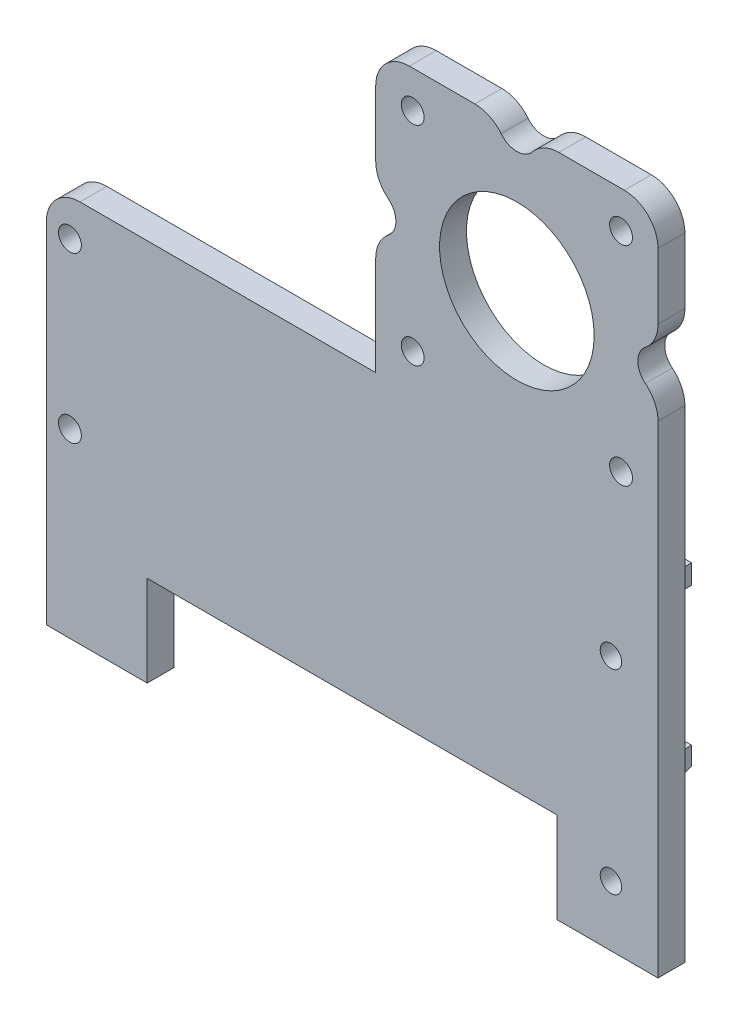
SolidWorks part; units mm, degrees
note: The reader was unsure of these and kept them because the rebuilt part matched: shared geometry of "草图1<4>", "草图1<5>".
ref_plane "前视基准面" through (0, 0, 0) normal (0, 0, 1) x (1, 0, 0)
ref_plane "上视基准面" through (0, 0, 0) normal (0, 1, 0) x (1, 0, 0)
ref_plane "右视基准面" through (0, 0, 0) normal (1, 0, 0) x (0, 0, -1)
sketch "草图1" plane through (0, 0, 0) normal (0, 0, 1) x (1, 0, 0)
  line L0 (0, -1000) -> (0, 49000) construction
  line L1 (-3.2, 10) -> (-3.2, 8.5) construction
  line L2 (-10, -10) -> (10, -10) construction
  line L3 (-10, -10) -> (-10, 10) construction
  line L4 (-10, 10) -> (10, 10) construction
  line L5 (-1000, 0) -> (49000, 0) construction
  line L6 (10, -10) -> (10, 10) construction
  line L7 (-10, -10) -> (10, 10) construction
  line L8 (-10, 10) -> (10, -10) construction
  line L9 (-3.2, 8.5) -> (-5.5, 8.5) construction
  line L10 (-5.5, 8.5) -> (-5.5, 6.7) construction
  line L11 (-5.5, 6.7) -> (-2.8, 4) construction
  line L12 (-2.8, 4) -> (2.8, 4) construction
  line L13 (5.5, 6.7) -> (2.8, 4) construction
  line L14 (5.5, 8.5) -> (5.5, 6.7) construction
  line L15 (3.2, 8.5) -> (5.5, 8.5) construction
  line L16 (3.2, 10) -> (3.2, 8.5) construction
  line L17 (8.5, 3.2) -> (8.5, 5.5) construction
  line L18 (8.5, 5.5) -> (6.7, 5.5) construction
  line L19 (6.7, 5.5) -> (4, 2.8) construction
  line L20 (4, 2.8) -> (4, -2.8) construction
  line L21 (6.7, -5.5) -> (4, -2.8) construction
  line L22 (8.5, -5.5) -> (6.7, -5.5) construction
  line L23 (8.5, -3.2) -> (8.5, -5.5) construction
  line L24 (10, 3.2) -> (8.5, 3.2) construction
  line L25 (10, -3.2) -> (8.5, -3.2) construction
  line L26 (3.2, -8.5) -> (5.5, -8.5) construction
  line L27 (5.5, -8.5) -> (5.5, -6.7) construction
  line L28 (5.5, -6.7) -> (2.8, -4) construction
  line L29 (2.8, -4) -> (-2.8, -4) construction
  line L30 (-5.5, -6.7) -> (-2.8, -4) construction
  line L31 (-5.5, -8.5) -> (-5.5, -6.7) construction
  line L32 (-3.2, -8.5) -> (-5.5, -8.5) construction
  line L33 (3.2, -10) -> (3.2, -8.5) construction
  line L34 (-3.2, -10) -> (-3.2, -8.5) construction
  line L35 (-8.5, -3.2) -> (-8.5, -5.5) construction
  line L36 (-8.5, -5.5) -> (-6.7, -5.5) construction
  line L37 (-6.7, -5.5) -> (-4, -2.8) construction
  line L38 (-4, -2.8) -> (-4, 2.8) construction
  line L39 (-6.7, 5.5) -> (-4, 2.8) construction
  line L40 (-8.5, 5.5) -> (-6.7, 5.5) construction
  line L41 (-8.5, 3.2) -> (-8.5, 5.5) construction
  line L42 (-10, -3.2) -> (-8.5, -3.2) construction
  line L43 (-10, 3.2) -> (-8.5, 3.2) construction
  line L44 (-10, 10) -> (-50, 10) construction
  line L45 (-50, 10) -> (-50, -10) construction
  line L46 (-50, -10) -> (-10, -10) construction
  line L47 (-50, -10) -> (21, -10)
  line L48 (-21, 30) -> (21, 30) construction
  line L49 (-21, 30) -> (-21, 44.755)
  line L50 (-16, 72) -> (-6.245, 72)
  line L51 (21, 30) -> (21, 44.755)
  line L52 (-21, 30) -> (21, 72) construction
  line L53 (-21, 72) -> (21, 30) construction
  line L54 (-50, 10) -> (-70, 10)
  line L55 (-50, -10) -> (-70, -10)
  line L56 (-50, -10) -> (-50, 13)
  line L57 (-50, 13) -> (-70, 13)
  line L58 (21, -10) -> (21, 30)
  line L59 (-21, 13) -> (-50, 13)
  line L60 (-50, 10) -> (10, 10)
  line L61 (-21, 13) -> (-21, 30)
  line L62 (6.245, 72) -> (16, 72)
  line L63 (-21, 57.245) -> (-21, 67)
  line L64 (21, 57.245) -> (21, 67)
  line L65 (-21, 13) -> (10, 13)
  line L66 (10, 13) -> (10, 10)
  line L67 (-50, -10) -> (-50, 10) construction
  line L68 (-24.55, 6) -> (-15.45, 6)
  line L69 (-50, 13) -> (-50, 10) construction
  line L70 (-3.05, 10) -> (-3.05, 8)
  line L71 (-3.05, 8) -> (-5.05, 8)
  line L72 (-5.05, 8) -> (-5.05, 6.5)
  line L73 (-5.05, 6.5) -> (-4.55, 6)
  line L74 (-4.55, 6) -> (4.55, 6)
  line L75 (5.05, 6.5) -> (4.55, 6)
  line L76 (5.05, 8) -> (5.05, 6.5)
  line L77 (3.05, 10) -> (3.05, 8)
  line L78 (3.05, 8) -> (5.05, 8)
  line L79 (-14.95, 6.5) -> (-15.45, 6)
  line L80 (-14.95, 8) -> (-14.95, 6.5)
  line L81 (-16.95, 8) -> (-14.95, 8)
  line L82 (-16.95, 10) -> (-16.95, 8)
  line L83 (-23.05, 10) -> (-23.05, 8)
  line L84 (-23.05, 8) -> (-25.05, 8)
  line L85 (-25.05, 8) -> (-25.05, 6.5)
  line L86 (-25.05, 6.5) -> (-24.55, 6)
  line L87 (-44.55, 6) -> (-35.45, 6)
  line L88 (-34.95, 6.5) -> (-35.45, 6)
  line L89 (-34.95, 8) -> (-34.95, 6.5)
  line L90 (-36.95, 8) -> (-34.95, 8)
  line L91 (-36.95, 10) -> (-36.95, 8)
  line L92 (-43.05, 10) -> (-43.05, 8)
  line L93 (-43.05, 8) -> (-45.05, 8)
  line L94 (-45.05, 8) -> (-45.05, 6.5)
  line L95 (-45.05, 6.5) -> (-44.55, 6)
  line L96 (-30, 10) -> (-30, -10) construction
  line L97 (-40, 10) -> (-40, -10) construction
  line L98 (-34, 4.55) -> (-34, -4.55)
  line L99 (-33.5, -5.05) -> (-34, -4.55)
  line L100 (-32, -5.05) -> (-33.5, -5.05)
  line L101 (-32, -3.05) -> (-32, -5.05)
  line L102 (-32, 3.05) -> (-28, 3.05)
  line L103 (-28, -3.05) -> (-32, -3.05)
  line L104 (-32, 3.05) -> (-32, 5.05)
  line L105 (-32, 5.05) -> (-33.5, 5.05)
  line L106 (-33.5, 5.05) -> (-34, 4.55)
  line L107 (-35.45, -6) -> (-44.55, -6)
  line L108 (-45.05, -6.5) -> (-44.55, -6)
  line L109 (-45.05, -8) -> (-45.05, -6.5)
  line L110 (-43.05, -8) -> (-45.05, -8)
  line L111 (-43.05, -10) -> (-43.05, -8)
  line L112 (-36.95, -10) -> (-36.95, -8)
  line L113 (-36.95, -8) -> (-34.95, -8)
  line L114 (-34.95, -8) -> (-34.95, -6.5)
  line L115 (-34.95, -6.5) -> (-35.45, -6)
  line L116 (-46, -4.55) -> (-46, 4.55) construction
  line L117 (-46.5, 5.05) -> (-46, 4.55) construction
  line L118 (-48, 5.05) -> (-46.5, 5.05) construction
  line L119 (-48, 3.05) -> (-48, 5.05) construction
  line L120 (-50, 3.05) -> (-48, 3.05) construction
  line L121 (-50, -3.05) -> (-48, -3.05) construction
  line L122 (-48, -3.05) -> (-48, -5.05) construction
  line L123 (-48, -5.05) -> (-46.5, -5.05) construction
  line L124 (-46.5, -5.05) -> (-46, -4.55) construction
  line L125 (-26.5, 5.05) -> (-26, 4.55)
  line L126 (-28, 5.05) -> (-26.5, 5.05)
  line L127 (-28, 3.05) -> (-28, 5.05)
  line L128 (-28, -3.05) -> (-28, -5.05)
  line L129 (-28, -5.05) -> (-26.5, -5.05)
  line L130 (-26.5, -5.05) -> (-26, -4.55)
  line L131 (-26, 4.55) -> (-26, -4.55)
  line L132 (-30, -3.05) -> (-32, -3.05) [skipped]
  line L133 (-30, 3.05) -> (-32, 3.05) [skipped]
  line L134 (-25.05, -6.5) -> (-24.55, -6)
  line L135 (-25.05, -8) -> (-25.05, -6.5)
  line L136 (-23.05, -8) -> (-25.05, -8)
  line L137 (-23.05, -10) -> (-23.05, -8)
  line L138 (-16.95, -10) -> (-16.95, -8)
  line L139 (-16.95, -8) -> (-14.95, -8)
  line L140 (-14.95, -8) -> (-14.95, -6.5)
  line L141 (-14.95, -6.5) -> (-15.45, -6)
  line L142 (-24.55, -6) -> (-15.45, -6)
  line L143 (-70, -10) -> (-70, 13)
  line L144 (-21, 30) -> (-70, 30)
  line L145 (-70, 30) -> (-70, 13)
  circle A0 centre (0, 51) radius 11.5
  circle A1 centre (15.5, 66.5) radius 1.7
  circle A2 centre (15.5, 35.5) radius 1.7
  circle A3 centre (-15.5, 35.5) radius 1.7
  circle A4 centre (-15.5, 66.5) radius 1.7
  arc A5 (16, 72) -> (21, 67) centre (16, 67) cw
  arc A6 (-21, 67) -> (-16, 72) centre (-16, 67) cw
  arc A7 (-2.3419, 70.125) -> (2.3419, 70.125) centre (0, 72) ccw
  arc A8 (-2.3419, 70.125) -> (-6.245, 72) centre (-6.245, 67) ccw
  arc A9 (2.3419, 70.125) -> (6.245, 72) centre (6.245, 67) cw
  arc A10 (19.125, 53.3419) -> (19.125, 48.6581) centre (21, 51) ccw
  arc A11 (19.125, 48.6581) -> (21, 44.755) centre (16, 44.755) cw
  arc A12 (19.125, 53.3419) -> (21, 57.245) centre (16, 57.245) ccw
  circle A13 centre (-66.5, 24.5) radius 1.7
  circle A14 centre (-66.5, 0) radius 1.7
  circle A15 centre (14, -18) radius 1.6
  arc A16 (-19.125, 48.6581) -> (-19.125, 53.3419) centre (-21, 51) ccw
  arc A17 (-19.125, 53.3419) -> (-21, 57.245) centre (-16, 57.245) cw
  arc A18 (-19.125, 48.6581) -> (-21, 44.755) centre (-16, 44.755) ccw
  circle A19 centre (14, 11) radius 1.6
  point P0 (0, 0)
  point P18 (0, 4)
  point P23 (0, 51)
  point P58 (0, 0)
  point P82 (0, 51)
  point P93 (3, 72)
  point P110 (0, 6)
  point P118 (0, 51)
  point P154 (-40, 0)
  point P176 (-40, 0)
  point P188 (-40, 0)
  dimension "D12" = 3
  dimension "D17" = 3.4
  dimension "D20" = 5
  dimension "D21" = 3
  dimension "D22" = 5
  dimension "D23" = 5
  dimension "D24" = 11.5
  dimension "D25" = 3.4
  dimension "D36" = 3.2
  dimension "D1" = 20
  dimension "D2" = 20
  dimension "D3" = 6.4
  dimension "D4" = 1.5
  dimension "D5" = 11
  dimension "D6" = 6
  dimension "D7" = 1.8
  dimension "D9" = 60
  dimension "D10" = 42
  dimension "D11" = 42
  dimension "D13" = 20
  dimension "D14" = 41
  dimension "D15" = 20
  dimension "D16" = 3
  dimension "D19" = 31
  dimension "D26" = 3.05
  dimension "D27" = 2
  dimension "D28" = 2
  dimension "D29" = 1.5
  dimension "D30" = 2
  dimension "D31" = 4.55
  dimension "D32" = 3.5
  dimension "D33" = 10
  dimension "D8" = 10
  dimension "D34" = 29
  dimension "D35" = 7
  dimension "D37" = 13.5
  dimension "D18" = 4
extrude "凸台-拉伸1" add sketch "草图1" along normal blind 4
extrude "凸台-拉伸2" add sketch "草图1<4>" against normal blind 12
sketch "草图1<4>" plane through (0, 0, 0) normal (0, 0, 1) x (1, 0, 0) same geometry as "草图1"
extrude "凸台-拉伸3" add sketch "草图1<5>" against normal blind 5 contours L78 L77 L60 L70 L71 L72 L73 L74 L75 L76 | L85 L86 L68 L79 L80 L81 L82 L60 L83 L84 | L94 L95 L87 L88 L89 L90 L91 L60 L92 L93 | L131 L125 L126 L127 L102 L104 L105 L106 L98 L99 L100 L101 L103 L128 L129 L130 | L142 L134 L135 L136 L137 L47 L138 L139 L140 L141 | L114 L115 L107 L108 L109 L110 L111 L47 L112 L113
sketch "草图1<5>" plane through (0, 0, 0) normal (0, 0, 1) x (1, 0, 0) same geometry as "草图1"
ref_plane "基准面1" [suppressed] through (0, 0, 0) normal (1, 0, 0) x (0, 0, -1)
sketch "草图4" plane through (10, 0, 0) normal (1, 0, 0) x (0, 0, -1)
  line L0 (10, 13) -> (0, 33)
  line L2 (0, 30) -> (0, 44.755) construction
  dimension "D2" = 10
rib "筋2" sketch "草图4" sketch "草图4" thickness 4 extrusion direction parallel to sketch draft on no parameters "D1"=4
mirror "镜向1" about plane through (0, 0, 0) normal (1, 0, 0) of "筋2"
sketch "草图5" plane through (0, 0, -12) normal (0, 0, -1) x (-1, 0, 0)
  line L0 (23.05, 10) -> (23.05, 8)
  line L1 (23.05, 8) -> (25.05, 8) construction
  line L2 (23.05, 8) -> (25.05, 8) construction
  line L3 (25.05, 8) -> (25.05, 6.5) construction
  line L4 (25.05, 8) -> (25.05, 6.5) construction
  line L5 (-1000, 0) -> (49000, 0) construction
  line L6 (30, -996.95) -> (30, 49003.05) construction
  line L7 (32, 3.05) -> (28, 3.05) construction
  line L8 (20, -993.9) -> (20, 49006.1) construction
  line L9 (24.55, 6) -> (15.45, 6) construction
  line L10 (40, -993.9) -> (40, 49006.1) construction
  line L11 (44.55, 6) -> (35.45, 6) construction
  line L12 (17.2, 10) -> (16.95, 10)
  line L13 (25.05, 7.75) -> (22.8, 7.75)
  line L14 (25.05, 8) -> (25.05, 7.75)
  line L15 (25.05, 8) -> (23.05, 8)
  line L16 (17.2, 7.75) -> (17.2, 10)
  line L17 (14.95, 8) -> (16.95, 8)
  line L18 (14.95, 8) -> (14.95, 7.75)
  line L19 (14.95, 7.75) -> (17.2, 7.75)
  line L20 (16.95, 10) -> (16.95, 8)
  line L21 (30, -990) -> (30, 49010) construction
  line L22 (70, 10) -> (-10, 10) construction
  line L23 (37.2, 10) -> (36.95, 10)
  line L24 (28, 5.05) -> (26.5, 5.05) construction
  line L25 (27.9, 5.05) -> (32.1, 5.05)
  line L26 (27.9, 5.05) -> (27.9, 3.05)
  line L27 (27.9, 3.05) -> (32.1, 3.05)
  line L28 (32.1, 5.05) -> (32.1, 3.05)
  line L29 (32, 3.05) -> (28, 3.05) construction
  line L30 (32, 3.05) -> (32, 5.05) construction
  line L31 (32.1, -5.05) -> (32.1, -3.05)
  line L32 (27.9, -3.05) -> (32.1, -3.05)
  line L33 (27.9, -5.05) -> (27.9, -3.05)
  line L34 (27.9, -5.05) -> (32.1, -5.05)
  line L35 (40, 993.9) -> (40, -49006.1) construction
  line L36 (20, 993.9) -> (20, -49006.1) construction
  line L37 (30, 996.95) -> (30, -49003.05) construction
  line L38 (37.2, 7.75) -> (37.2, 10)
  line L39 (43.05, 10) -> (43.05, 8)
  line L40 (45.05, 7.75) -> (42.8, 7.75)
  line L41 (45.05, 8) -> (45.05, 7.75)
  line L42 (45.05, 8) -> (43.05, 8)
  line L43 (42.8, 7.75) -> (42.8, 10)
  line L44 (34.95, 8) -> (36.95, 8)
  line L45 (34.95, 8) -> (34.95, 7.75)
  line L46 (34.95, 7.75) -> (37.2, 7.75)
  line L47 (42.8, 10) -> (43.05, 10)
  line L48 (36.95, 10) -> (36.95, 8)
  line L49 (37.2, 10) -> (36.95, 10)
  line L50 (37.2, 7.75) -> (37.2, 10)
  line L51 (43.05, 10) -> (43.05, 8)
  line L52 (45.05, 7.75) -> (42.8, 7.75)
  line L53 (45.05, 8) -> (45.05, 7.75)
  line L54 (45.05, 8) -> (43.05, 8)
  line L55 (22.8, 7.75) -> (22.8, 10)
  line L56 (22.8, 10) -> (23.05, 10)
  line L57 (42.8, 7.75) -> (42.8, 10)
  line L58 (34.95, 8) -> (36.95, 8)
  line L59 (34.95, 8) -> (34.95, 7.75)
  line L60 (34.95, 7.75) -> (37.2, 7.75)
  line L61 (42.8, 10) -> (43.05, 10)
  line L62 (36.95, 10) -> (36.95, 8)
  line L63 (70, 10) -> (70, 13) construction
  line L64 (-10, 10) -> (37.2, 10)
  line L65 (-10, 10) -> (-10, 10.1)
  line L66 (-10, 10.1) -> (37.2, 10.1)
  line L67 (37.2, 10) -> (37.2, 10.1)
  line L68 (42.8, 10) -> (17.2, 10)
  line L69 (42.8, 10) -> (42.8, 10.1)
  line L70 (42.8, 10.1) -> (17.2, 10.1)
  line L71 (17.2, 10) -> (17.2, 10.1)
  line L72 (22.8, 10) -> (37.2, 10)
  line L73 (22.8, 10) -> (22.8, 10.1)
  line L74 (22.8, 10.1) -> (37.2, 10.1)
  line L75 (37.2, 10) -> (37.2, 10.1)
  line L76 (42.8, 10) -> (70, 10)
  line L77 (42.8, 10) -> (42.8, 10.1)
  line L78 (42.8, 10.1) -> (70, 10.1)
  line L79 (70, 10) -> (70, 10.1)
  line L80 (3.05, 10) -> (3.05, 10.1)
  line L81 (-3.05, 10) -> (-3.05, 10.1)
  point P15 (30, 3.05)
  point P20 (20, 6)
  point P25 (40, 6)
  point P60 (30, 10)
  line M126 (-10, 13) -> (-10, 10)
  line M127 (-10, 10) -> (70, 10)
  line M128 (70, 10) -> (70, 13)
  dimension "D1" = 0.25
  dimension "D2" = 0.1
  dimension "D3" = 0.25
  dimension "D4" = 0.1
extrude "切除-拉伸5" cut sketch "草图5" against normal up to surface (12 mm away) contours L81 L66 M127 M126 | L80 L64 L71 L66 M127 | L20 L17 L18 L19 L16 M127 | L55 L13 L14 L15 L0 M127 | L73 L67 L70 M127 | L78 L69 M127 M128 | L43 L40 L41 L42 L39 M127 | L48 L44 L45 L46 L38 M127
chamfer "倒角3" distance 0.8 angle 20 27 edges at (-42.8, 8.875, -5) (-37.2, 8.875, -5) (-36.075, 7.75, -5) (-34.95, 7.125, -5) (-35.2, 6.25, -5) (-40, 6, -5) (-44.8, 6.25, -5) (-45.05, 7.125, -5) (-43.925, 7.75, -5) (-22.8, 8.875, -5) (-23.925, 7.75, -5) (-25.05, 7.125, -5) (-24.8, 6.25, -5) (-17.2, 8.875, -5) (-16.075, 7.75, -5) (-14.95, 7.125, -5) (-15.2, 6.25, -5) (-20, 6, -5) (-3.05, 9, -5) (-4.05, 8, -5) (-5.05, 7.25, -5) (-4.8, 6.25, -5) (0, 6, -5) (4.8, 6.25, -5) (5.05, 7.25, -5) (4.05, 8, -5) (3.05, 9, -5)
sketch "草图6" plane through (0, 0, 4) normal (0, 0, 1) x (1, 0, 0)
  line L0 (21, -10) -> (21, 44.755) construction
  line L1 (-70, -10) -> (21, -10)
  line L2 (-70, -10) -> (-70, -27)
  line L3 (-70, -27) -> (21, -27)
  line L4 (21, -10) -> (21, -27)
  line L5 (-70, -10) -> (-70, 30) construction
  line L6 (-21, 30) -> (21, 30) construction
  line L7 (-21, 30) -> (-21, 72) construction
  line L8 (-21, 72) -> (21, 72) construction
  line L9 (21, 30) -> (21, 72) construction
  line L10 (-21, 30) -> (21, 72) construction
  line L11 (-21, 72) -> (21, 30) construction
  point P7 (0, 51)
  dimension "D1" = 57
  dimension "D2" = 17
extrude "凸台-拉伸4" add sketch "草图6" against normal up to surface (4 mm away)
sketch "草图7" plane through (0, 0, 0) normal (0, 0, -1) x (-1, 0, 0)
  line L1 (-10, -10) -> (70, -10)
  line L2 (-10, -10) -> (-10, -13.5)
  line L3 (-10, -13.5) -> (70, -13.5)
  line L4 (70, -10) -> (70, -13.5)
  line L5 (23.05, -10) -> (16.95, -10) construction
  line L6 (-10, 13) -> (-10, 10.1) construction
  line L7 (70, -27) -> (70, 10.1) construction
  dimension "D1" = 3.5
extrude "凸台-拉伸5" add sketch "草图7" along normal blind 12
sketch "草图8" plane through (0, 0, 0) normal (0, 0, -1) x (-1, 0, 0)
  line L0 (-10, -13.5) -> (70, -13.5) construction
  line L1 (55, -13.5) -> (-6, -13.5)
  line L2 (55, -13.5) -> (55, -27)
  line L3 (55, -27) -> (-6, -27)
  line L4 (-21, -27) -> (70, -27) construction
  line L5 (-21, -27) -> (70, -27) construction
  line L6 (-21, 30) -> (21, 30) construction
  line L7 (-6, -27) -> (-6, -13.5)
  line L8 (70, -27) -> (70, -13.5) construction
  line L9 (21, 30) -> (21, 44.755) construction
  line L10 (70, -27) -> (-21, -27) construction
  line L11 (-21, -27) -> (-21, 44.755) construction
  line L14 (16, 72) -> (6.245, 72) construction
  circle A0 centre (-14, -18) radius 1.6
  point P12 (-14, 11)
  dimension "D4" = 3.2
  dimension "D5" = 29
  dimension "D1" = 15
  dimension "D2" = 15
  dimension "D3" = 42
extrude "切除-拉伸3" cut sketch "草图8" against normal through all
sketch "草图9" plane through (0, 0, -12) normal (0, 0, -1) x (-1, 0, 0)
  line L0 (70, -13.5) -> (70, -10) construction
  line L1 (50, -10) -> (25.4529, -10)
  line L2 (50, -10) -> (50, 5.5862)
  line L3 (50, 5.5862) -> (25.4529, 5.5862)
  line L4 (25.4529, 0.3648) -> (25.4529, 5.5862)
  line L5 (25.4529, 0.3648) -> (11.1226, 0.3648)
  line L6 (11.1226, 0.3648) -> (11.1226, -10)
  line L7 (16.95, -10) -> (-10, -10) construction
  line L8 (11.1226, -10) -> (25.4529, -10)
  line L9 (-10, -10) -> (70, -10)
  line L10 (-10, -10) -> (-10, -10.5)
  line L11 (-10, -10.5) -> (70, -10.5)
  line L12 (70, -10) -> (70, -10.5)
  dimension "D1" = 0.5
extrude "切除-拉伸4" cut sketch "草图9" against normal up to surface (12 mm away)
chamfer "倒角2" distance 0.8 angle 20 1 edges at (-30, -13.5, -12)
sketch "草图10" plane through (0, -13.5, 0) normal (0, -1, 0) x (1, 0, 0)
  circle A0 centre (-60, -8) radius 2.2
  circle A1 centre (0, -8) radius 2.2
  dimension "D1" = 4.4
  dimension "D2" = 4.4
  dimension "D3" = 4
  dimension "D4" = 10
extrude "切除-拉伸6" cut sketch "草图10" against normal through all
fillet "圆角1" radius 5 1 edges at (-70, 30, 2)
